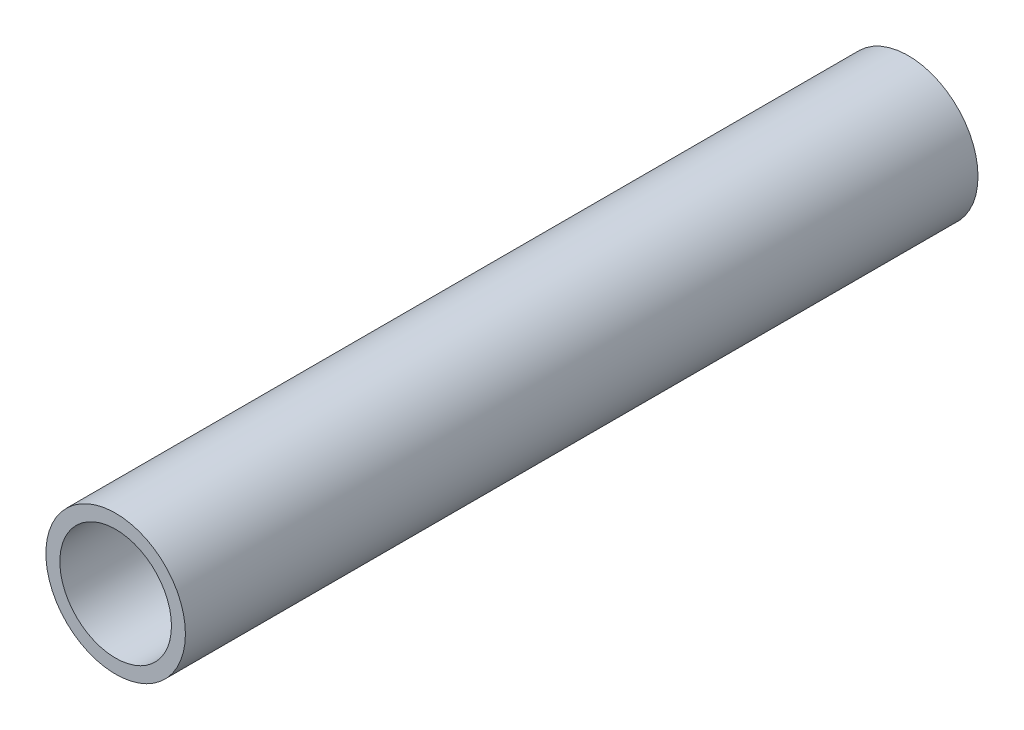
SolidWorks part; units mm, degrees
ref_plane "Front Plane" through (0, 0, 0) normal (0, 0, 1) x (1, 0, 0)
ref_plane "Top Plane" through (0, 0, 0) normal (0, 1, 0) x (1, 0, 0)
ref_plane "Right Plane" through (0, 0, 0) normal (1, 0, 0) x (0, 0, -1)
sketch "Sketch1" plane through (0, 0, 0) normal (0, 0, 1) x (1, 0, 0)
  circle A0 centre (0, 0) radius 1.25
  circle A1 centre (0, 0) radius 1
extrude "Boss-Extrude1" add sketch "Sketch1" along normal blind 14.2
